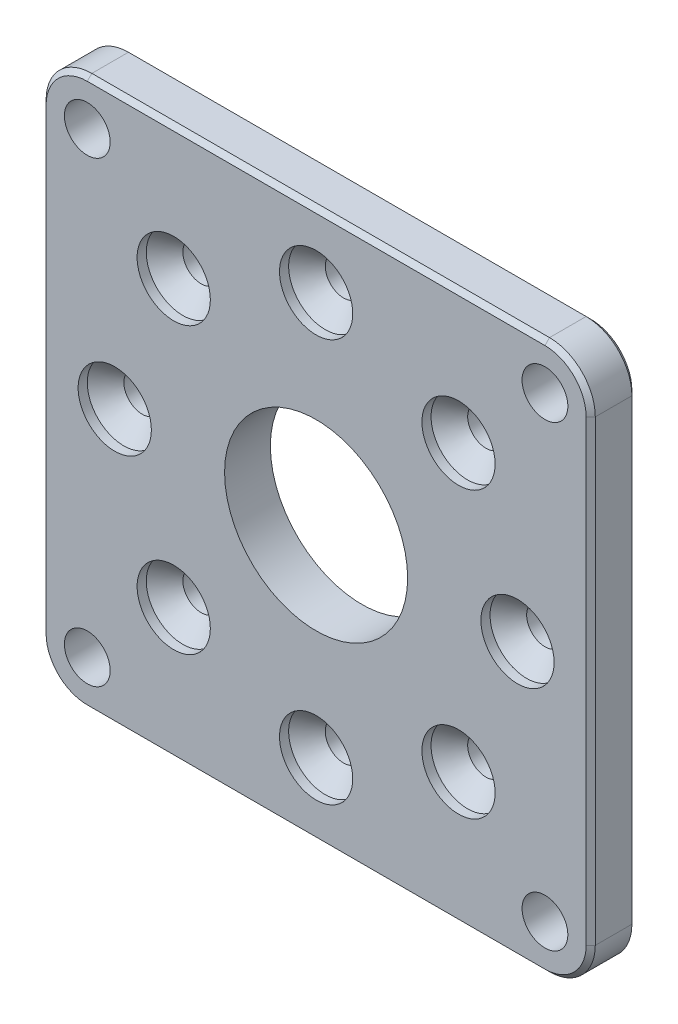
SolidWorks part; units mm, degrees
material "7075-T6，板材(SS)"
ref_plane "前视基准面" through (0, 0, 0) normal (0, 0, 1) x (1, 0, 0)
ref_plane "上视基准面" through (0, 0, 0) normal (0, 1, 0) x (1, 0, 0)
ref_plane "右视基准面" through (0, 0, 0) normal (1, 0, 0) x (0, 0, -1)
sketch "草图1" plane through (0, 0, 0) normal (0, 0, 1) x (1, 0, 0)
  line L0 (-30, 0) -> (30, 0) construction
  line L1 (-25, -30) -> (25, -30)
  line L2 (-30, -25) -> (-30, 25)
  line L3 (-25, 30) -> (25, 30)
  line L4 (30, -25) -> (30, 25)
  line L5 (-30, -30) -> (30, 30) construction
  line L6 (-30, 30) -> (30, -30) construction
  line L7 (0, 30) -> (0, -30) construction
  arc A0 (25, 30) -> (30, 25) centre (25, 25) cw
  arc A1 (25, -30) -> (30, -25) centre (25, -25) ccw
  arc A2 (-25, -30) -> (-30, -25) centre (-25, -25) cw
  arc A3 (-30, 25) -> (-25, 30) centre (-25, 25) cw
  circle A4 centre (-25, 25) radius 2.5
  circle A5 centre (-25, -25) radius 2.5
  circle A6 centre (25, -25) radius 2.5
  circle A7 centre (25, 25) radius 2.5
  circle A8 centre (0, 0) radius 10
  circle A9 centre (-15.5563, 15.5563) radius 2
  circle A10 centre (0, 22) radius 2
  circle A11 centre (15.5563, 15.5563) radius 2
  circle A12 centre (22, 0) radius 2
  circle A13 centre (0, 0) radius 22 construction
  circle A14 centre (15.5563, -15.5563) radius 2
  circle A15 centre (0, -22) radius 2
  circle A16 centre (-15.5563, -15.5563) radius 2
  circle A17 centre (-22, 0) radius 2
  circle A18 centre (0, 15) radius 2 construction
  circle A19 centre (10.6066, 10.6066) radius 2 construction
  circle A20 centre (15, 0) radius 2 construction
  circle A21 centre (10.6066, -10.6066) radius 2 construction
  circle A22 centre (0, -15) radius 2 construction
  circle A23 centre (-10.6066, -10.6066) radius 2 construction
  circle A24 centre (-15, 0) radius 2 construction
  circle A25 centre (-10.6066, 10.6066) radius 2 construction
  circle A26 centre (0, 0) radius 15 construction
  point P0 (0, 0)
  dimension "D2" = 5
  dimension "D3" = 50
  dimension "D4" = 5
  dimension "D5" = 20
  dimension "D6" = 4
  dimension "D8" = 44
  dimension "D10" = 30
  dimension "D1" = 60
  dimension "D9" = 8
  dimension "D7" = 8
extrude "凸台-拉伸1" add sketch "草图1" along normal blind 5
sketch "草图2" plane through (0, 0, 5) normal (0, 0, 1) x (1, 0, 0)
  circle A73 centre (-15.5563, 15.5563) radius 4
  circle A74 centre (0, 22) radius 4
  circle A75 centre (15.5563, 15.5563) radius 4
  circle A76 centre (22, 0) radius 4
  circle A77 centre (15.5563, -15.5563) radius 4
  circle A78 centre (0, -22) radius 4
  circle A79 centre (-15.5563, -15.5563) radius 4
  circle A80 centre (-22, 0) radius 4
  dimension "D1" = 8
  dimension "D2" = 8
extrude "切除-拉伸1" cut sketch "草图2" against normal blind 1
chamfer "倒角1" distance 2 angle 45 8 edges at (-13.5563, -15.5563, 4) (-13.5563, 15.5563, 4) (17.5563, 15.5563, 4) (17.5563, -15.5563, 4) (2, 22, 4) (24, 0, 4) (2, -22, 4) (-20, 0, 4)
chamfer "Chamfer1" distance 0.5 angle 45 16 edges at (0, -30, 0) (28.5355, -28.5355, 0) (-28.5355, -28.5355, 0) (30, 0, 0) (-30, 0, 0) (28.5355, 28.5355, 0) (-28.5355, 28.5355, 0) (0, 30, 0) (0, -30, 5) (28.5355, -28.5355, 5) (-28.5355, -28.5355, 5) (30, 0, 5) (-30, 0, 5) (28.5355, 28.5355, 5) (-28.5355, 28.5355, 5) (0, 30, 5)
